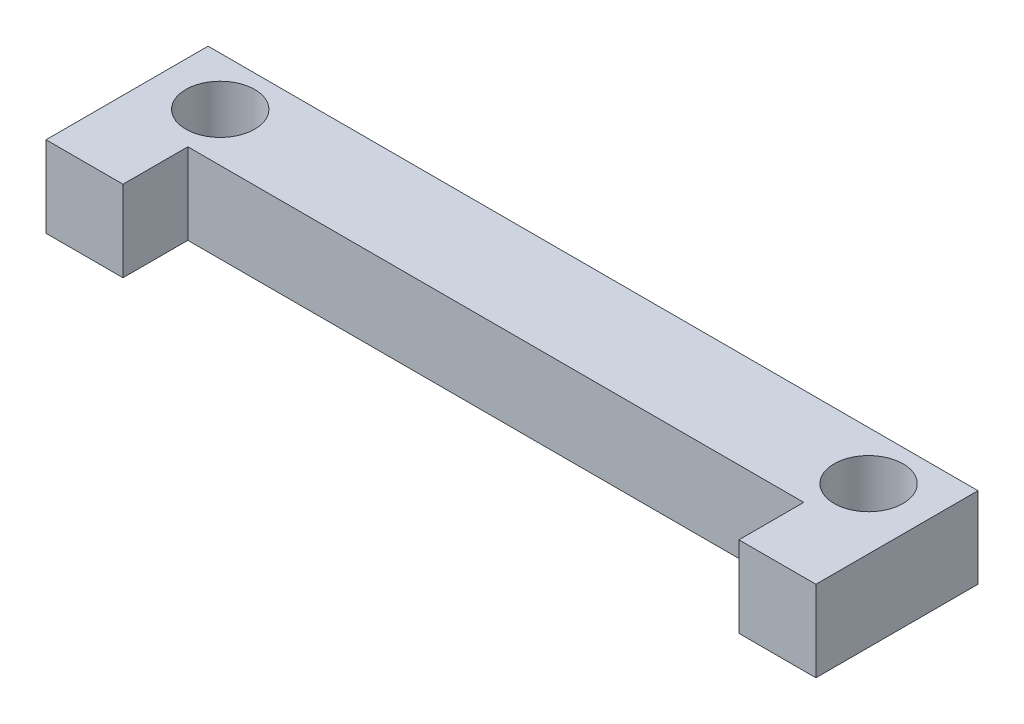
SolidWorks part; units mm, degrees
ref_plane "Front Plane" through (0, 0, 0) normal (0, 0, 1) x (1, 0, 0)
ref_plane "Top Plane" through (0, 0, 0) normal (0, 1, 0) x (1, 0, 0)
ref_plane "Right Plane" through (0, 0, 0) normal (1, 0, 0) x (0, 0, -1)
sketch "Sketch1" plane through (0, 0, 0) normal (0, 1, 0) x (1, 0, 0)
  line L0 (-55, 0) -> (55, 0) construction
  line L1 (-47.5, 12) -> (47.5, 12)
  line L3 (-38, 0) -> (38, 0)
  line L4 (47.5, 12) -> (47.5, 0)
  line L8 (-47.5, -8) -> (-38, -8)
  line L9 (-38, -8) -> (-38, 0)
  line L10 (0, -55) -> (0, 55) construction
  line L11 (47.5, -8) -> (38, -8)
  line L12 (38, -8) -> (38, 0)
  line L13 (47.5, 0) -> (47.5, -8)
  line L14 (-40, 6) -> (-40, 12) construction
  line L15 (-40, 6) -> (-40, 0) construction
  line L19 (-47.5, 12) -> (-47.5, -8)
  circle A0 centre (-40, 6) radius 4.25
  circle A1 centre (40, 6) radius 4.25
  point P2 (0, 0)
  point P6 (0, 0)
  dimension "D2" = 8.5
  dimension "D1" = 95
  dimension "D3" = 76
  dimension "D4" = 20
  dimension "D5" = 80
  dimension "D6" = 6
  dimension "D7" = 7.5
extrude "Boss-Extrude1" add sketch "Sketch1" along normal blind 10
